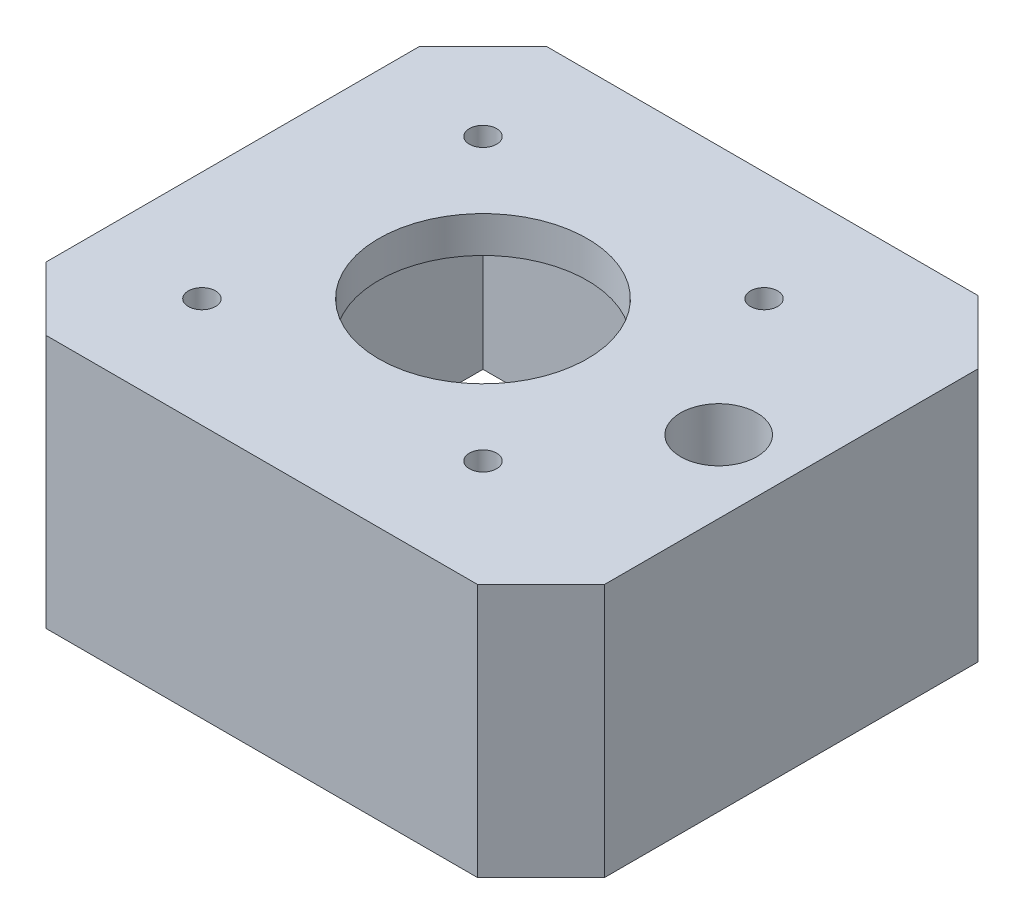
SolidWorks part; units mm, degrees
ref_plane "Front Plane" through (0, 0, 0) normal (0, 0, 1) x (1, 0, 0)
ref_plane "Top Plane" through (0, 0, 0) normal (0, 1, 0) x (1, 0, 0)
ref_plane "Right Plane" through (0, 0, 0) normal (1, 0, 0) x (0, 0, -1)
sketch "Sketch1" plane through (0, 0, 0) normal (0, 1, 0) x (1, 0, 0)
  line L0 (0, 21) -> (55, 21) construction
  line L1 (0, 0) -> (55, 0)
  line L2 (0, 0) -> (0, 42)
  line L3 (0, 42) -> (55, 42)
  line L4 (55, 0) -> (55, 42)
  line L5 (21, 42) -> (21, 0) construction
  circle A0 centre (47, 21) radius 4.2
  circle A1 centre (21, 21) radius 11.5
  circle A2 centre (5.5, 36.5) radius 1.5
  circle A3 centre (36.5, 36.5) radius 1.5
  circle A4 centre (5.5, 5.5) radius 1.5
  circle A5 centre (36.5, 5.5) radius 1.5
  point P8 (55, 21)
  dimension "D2" = 23
  dimension "D4" = 8.4
  dimension "D9" = 3
  dimension "D1" = 26
  dimension "D3" = 42
  dimension "D5" = 21
  dimension "D6" = 55
  dimension "D7" = 15.5
  dimension "D8" = 15.5
extrude "Boss-Extrude1" add sketch "Sketch1" along normal blind 4
sketch "Sketch2" plane through (0, 0, 0) normal (0, -1, 0) x (1, 0, 0)
  line L0 (0, 0) -> (55, 0) construction
  line L1 (40.4, 0) -> (42.25, 0)
  line L2 (40.4, 0) -> (40.4, -42)
  line L3 (40.4, -42) -> (42.25, -42)
  line L4 (42.25, 0) -> (42.25, -42)
  line L5 (55, -42) -> (0, -42) construction
  line L6 (55, 0) -> (55, -42) construction
  line L7 (55, -11) -> (42.25, -11)
  line L8 (55, -11) -> (55, -31)
  line L9 (55, -31) -> (42.25, -31)
  line L10 (42.25, -11) -> (42.25, -31)
  circle A0 centre (47, -21) radius 6.6
  circle A1 centre (47, -21) radius 4.2
  circle A2 centre (47, -21) radius 4.2 construction
  point P25 (55, -21)
  point P26 (55, -21)
  circle M7 centre (47, -21) radius 4.2
  line M10 (55, -42) -> (55, 0)
  dimension "D1" = 2.4
  dimension "D2" = 1.85
  dimension "D3" = 20
extrude "Boss-Extrude2" add sketch "Sketch2" along normal blind 20 contours L4 A0 L10 M7 | A0 L10 L9 L7 L4 M10 region at (48.625, 0, -11.2372) region at (49.4057, 0, -15.0414)
sketch "Sketch3" plane through (0, -20, 0) normal (0, -1, 0) x (1, 0, 0)
  line L1 (55, -31) -> (42.25, -31)
  line L2 (55, -31) -> (55, -11)
  line L3 (55, -11) -> (42.25, -11)
  line L4 (42.25, -31) -> (42.25, -11)
extrude "Boss-Extrude3" add sketch "Sketch3" along normal blind 4
sketch "Sketch4" plane through (0, 0, 0) normal (0, -1, 0) x (1, 0, 0)
  line L0 (42.25, -11) -> (42.25, -31) construction
  line L1 (42.25, 0.25) -> (-0.25, 0.25)
  line L2 (42.25, 0.25) -> (42.25, -42.25)
  line L3 (42.25, -42.25) -> (-0.25, -42.25)
  line L4 (-0.25, 0.25) -> (-0.25, -42.25)
  line L9 (48.6, 6.6) -> (-6.6, 6.6)
  line L10 (48.6, 6.6) -> (48.6, -48.6)
  line L11 (48.6, -48.6) -> (-6.6, -48.6)
  line L12 (-6.6, 6.6) -> (-6.6, -48.6)
  line L13 (55, -42) -> (0, -42) construction
  line L14 (0, -42) -> (0, 0) construction
  line L15 (0, 0) -> (55, 0) construction
  point P10 (-0.8165, -44.7067)
  dimension "D1" = 0.25
  dimension "D2" = 0.25
  dimension "D3" = 0.25
  dimension "D4" = 6.35
  dimension "D5" = 6.35
  dimension "D6" = 6.35
  dimension "D7" = 6.35
extrude "Boss-Extrude4" add sketch "Sketch4" along normal up to surface (24 mm away) contours L10 L9 L12 L11 | L2 L1 L4 L3 up to face at (48.625, -24, -21)
sketch "Sketch5" plane through (0, 0, 0) normal (0, 1, 0) x (1, 0, 0)
  circle A0 centre (47, 21) radius 4.2
  circle A1 centre (47, 21) radius 4.2 construction
extrude "Cut-Extrude1" cut sketch "Sketch5" against normal up to surface (20 mm away) up to face at (49.9, -20, -21)
sketch "Sketch6" plane through (48.6, 0, 0) normal (1, 0, 0) x (0, 0, -1)
  line L0 (0, 4) -> (42, 4) construction
  line L1 (-6.6, 0) -> (0, 0)
  line L2 (-6.6, 0) -> (-6.6, 4)
  line L3 (-6.6, 4) -> (0, 4)
  line L4 (0, 0) -> (0, 4)
  line L5 (0, 4) -> (42, 4)
  line L6 (21, 4) -> (21, -2.4275) construction
  line L7 (48.6, 4) -> (42, 4)
  line L8 (42, 0) -> (42, 4)
  line L9 (48.6, 0) -> (42, 0)
  line L10 (48.6, 0) -> (48.6, 4)
  point P9 (21, 4)
  line M3 (0, 0) -> (-6.6, 0)
extrude "Boss-Extrude6" add sketch "Sketch6" against normal up to surface (48.6 mm away) contours L9 L10 L7 L8 | L4 L3 L2 M3 region at (48.6, 2, 3.3) region at (48.6, 2, -45.3) up to face at (0, 2, -21)
sketch "Sketch7" plane through (0, 0, -48.6) normal (0, 0, -1) x (-1, 0, 0)
  line L0 (6.6, -24) -> (6.6, 0) construction
  line L1 (0, 0) -> (6.6, 0)
  line L2 (0, 0) -> (0, 4)
  line L3 (0, 4) -> (6.6, 4)
  line L4 (6.6, 0) -> (6.6, 4)
  point P5 (0, 4)
  point P7 (6.6, 0)
extrude "Boss-Extrude7" add sketch "Sketch7" against normal up to surface (55.2 mm away) up to face at (14, -6.6667, 6.6)
sketch "Sketch8" plane through (48.6, 0, 0) normal (1, 0, 0) x (0, 0, -1)
  line L6 (42, 0) -> (31, 0)
  line L7 (31, 0) -> (31, -24)
  line L8 (31, -24) -> (48.6, -24)
  line L9 (48.6, -24) -> (48.6, 4)
  line L10 (48.6, 4) -> (42, 4)
  line L11 (42, 4) -> (42, 0)
  line L12 (42, 0) -> (31, 0)
  line L13 (31, 0) -> (31, -24)
  line L14 (31, -24) -> (48.6, -24)
  line L15 (48.6, -24) -> (48.6, 4)
  line L16 (48.6, 4) -> (42, 4)
  line L17 (42, 4) -> (42, 0)
  line L18 (11, -24) -> (11, 0)
  line L19 (11, 0) -> (0, 0)
  line L20 (0, 0) -> (0, 4)
  line L21 (0, 4) -> (-6.6, 4)
  line L22 (-6.6, 4) -> (-6.6, -24)
  line L23 (-6.6, -24) -> (11, -24)
  line L24 (11, -24) -> (11, 0)
  line L25 (11, 0) -> (0, 0)
  line L26 (0, 0) -> (0, 4)
  line L27 (0, 4) -> (-6.6, 4)
  line L28 (-6.6, 4) -> (-6.6, -24)
  line L29 (-6.6, -24) -> (11, -24)
  dimension "D1" = 0
  dimension "D2" = 0
extrude "Boss-Extrude8" add sketch "Sketch8" along normal up to surface (6.4 mm away) up to face at (55, -5, -21)
sketch "Sketch9" plane through (0, 4, 0) normal (0, 1, 0) x (1, 0, 0)
  line L0 (55, 0.4) -> (48, -6.6)
  line L1 (55, -6.6) -> (55, 48.6) construction
  line L2 (-6.6, -6.6) -> (55, -6.6) construction
  line L3 (48, -6.6) -> (55, -6.6)
  line L4 (55, -6.6) -> (55, 0.4)
  line L5 (55, 41.6) -> (48, 48.6)
  line L6 (-6.6, 48.6) -> (55, 48.6) construction
  line L7 (48, 48.6) -> (55, 48.6)
  line L8 (55, 48.6) -> (55, 41.6)
  line L9 (0.4, 48.6) -> (-6.6, 48.6)
  line L10 (-6.6, 48.6) -> (-6.6, 41.6)
  line L11 (-6.6, -6.6) -> (-6.6, 48.6) construction
  line L12 (-6.6, 41.6) -> (0.4, 48.6)
  line L13 (0.4, -6.6) -> (-6.6, 0.4)
  line L14 (-6.6, 0.4) -> (-6.6, -6.6)
  line L15 (-6.6, -6.6) -> (0.4, -6.6)
  dimension "D1" = 7
extrude "Cut-Extrude2" cut sketch "Sketch9" against normal up to surface (28 mm away) up to face at (24.2, -24, -21)
equation "\"8mm hole\" = 8.4mm"
equation "\"22mm hole\"= 23mm"
equation "\"D2@Sketch1\"=\"22mm hole\""
equation "\"D4@Sketch1\"=\"8mm hole\""
